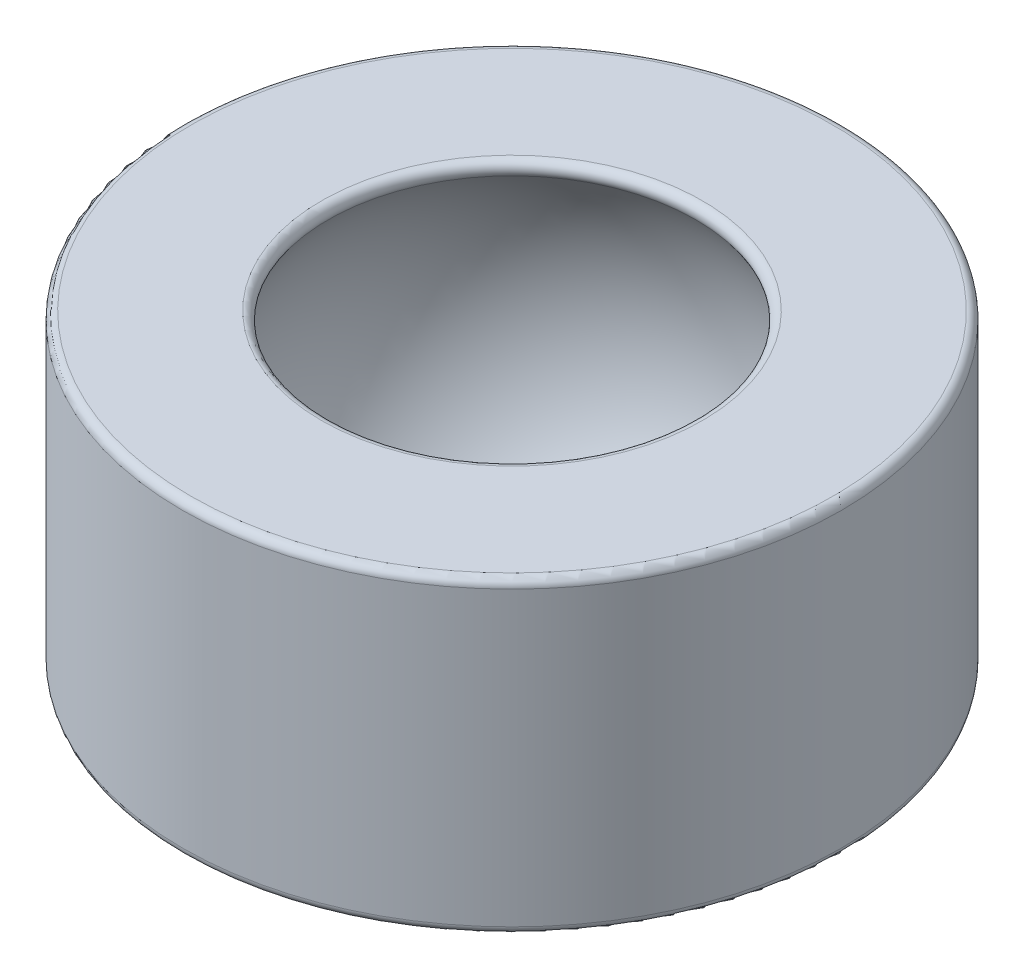
SolidWorks part; units mm, degrees
ref_plane "Front Plane" through (0, 0, 0) normal (0, 0, 1) x (1, 0, 0)
ref_plane "Top Plane" through (0, 0, 0) normal (0, 1, 0) x (1, 0, 0)
ref_plane "Right Plane" through (0, 0, 0) normal (1, 0, 0) x (0, 0, -1)
sketch "Sketch2" plane through (0, 0, 0) normal (0, 1, 0) x (1, 0, 0)
  circle A0 centre (0, 0) radius 2
  circle A1 centre (0, 0) radius 3 construction
  circle A2 centre (0, 0) radius 4
  dimension "D1" = 4
  dimension "D2" = 6
  dimension "D3" = 8
extrude "Boss-Extrude1" add sketch "Sketch2" along normal blind 1.875 and the other way blind 1.875
sketch "Sketch4" plane through (0, 0, 0) normal (0, 1, 0) x (1, 0, 0)
  line L0 (0, 2.8147) -> (0, -2.8147)
  arc A0 (0, 2.8147) -> (0, -2.8147) centre (0, 0) ccw
revolve "Revolve1" add sketch "Sketch4" angle 360 about L0
combine bodies "Combine2" operation type subtract main body 101 bodies to subtract 102
fillet "Fillet1" radius 0.1 4 edges at (0, -1.875, 4) (0, 1.875, 4) (0, -1.875, 2.0993) (0, 1.875, 2.0993)
